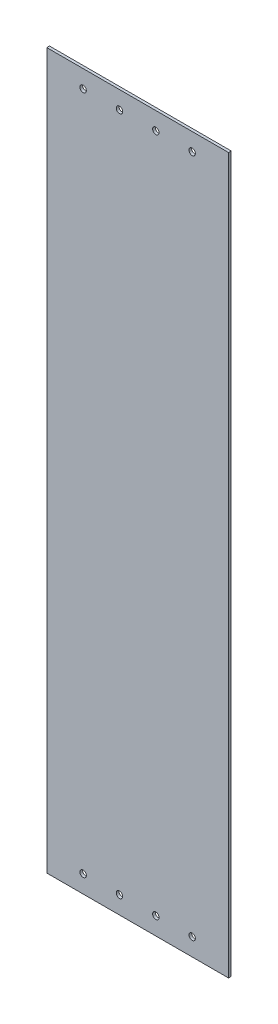
SolidWorks part; units mm, degrees
material "5052-H32"
ref_plane "Front Plane" through (0, 0, 0) normal (0, 0, 1) x (1, 0, 0)
ref_plane "Top Plane" through (0, 0, 0) normal (0, 1, 0) x (1, 0, 0)
ref_plane "Right Plane" through (0, 0, 0) normal (1, 0, 0) x (0, 0, -1)
sketch "Sketch1" plane through (0, 0, 0) normal (0, 0, 1) x (1, 0, 0)
  line L0 (55, 0) -> (-55, 0) construction
  line L1 (-77.5, 304.8) -> (77.5, 304.8)
  line L2 (-77.5, 304.8) -> (-77.5, -304.8)
  line L3 (-77.5, -304.8) -> (77.5, -304.8)
  line L4 (77.5, 304.8) -> (77.5, -304.8)
  line L5 (-77.5, 304.8) -> (77.5, -304.8) construction
  line L6 (-77.5, -304.8) -> (77.5, 304.8) construction
  point P0 (0, 0)
  point P20 (-46.5, 289.795)
  point P21 (-15.5, 289.795)
  point P23 (15.5, 289.795)
  point P24 (46.5, 289.795)
  point P25 (46.5, 296.2705)
  point P26 (0, 0)
  point P27 (0, 0)
  point P28 (0, 0)
  point P29 (0, 0)
  point P30 (0, 0)
  point P33 (46.5, -289.795)
  point P34 (15.5, -289.795)
  point P35 (-15.5, -289.795)
  point P36 (-46.5, -289.795)
  point P37 (0, 0)
  point P38 (0, 0)
  point P39 (0, 0)
  point P40 (0, 0)
  point P41 (0, 0)
  point P42 (0, 0)
  dimension "D1" = 609.6
  dimension "D2" = 155
  dimension "D20" = 31
  dimension "D21" = 31
  dimension "D22" = 31
  dimension "D23" = 31
  dimension "D24" = 15.005
extrude "Boss-Extrude1" add sketch "Sketch1" along normal blind 2.305
hole_wizard "M5 Clearance Hole1" positions "Sketch2" profile "Sketch3" hole size "M5" standard "ANSI Metric" end condition through all
sketch "Sketch2" plane through (0, 0, 2.305) normal (0, 0, 1) x (1, 0, 0)
  point P0 (-46.5, 289.795)
  point P3 (-15.5, 289.795)
  point P6 (15.5, 289.795)
  point P9 (46.5, 289.795)
  point P12 (-46.5, -289.795)
  point P15 (-15.5, -289.795)
  point P18 (15.5, -289.795)
  point P21 (46.5, -289.795)
sketch "Sketch3" plane through (-46.5, 289.795, 2.305) normal (1, 0, 0) x (0, -1, 0)
  line L0 (0, 0) -> (0, 2.305)
  line L1 (0, 2.305) -> (2.75, 2.305)
  line L2 (2.75, 2.305) -> (2.75, 0)
  line L5 (2.75, 0) -> (0, 0)
  line L11 (0, -6.35) -> (0, 107.95) construction
  dimension "Thru Hole Dia." = 5.5
  dimension "Thru Hole Depth" = 2.305
